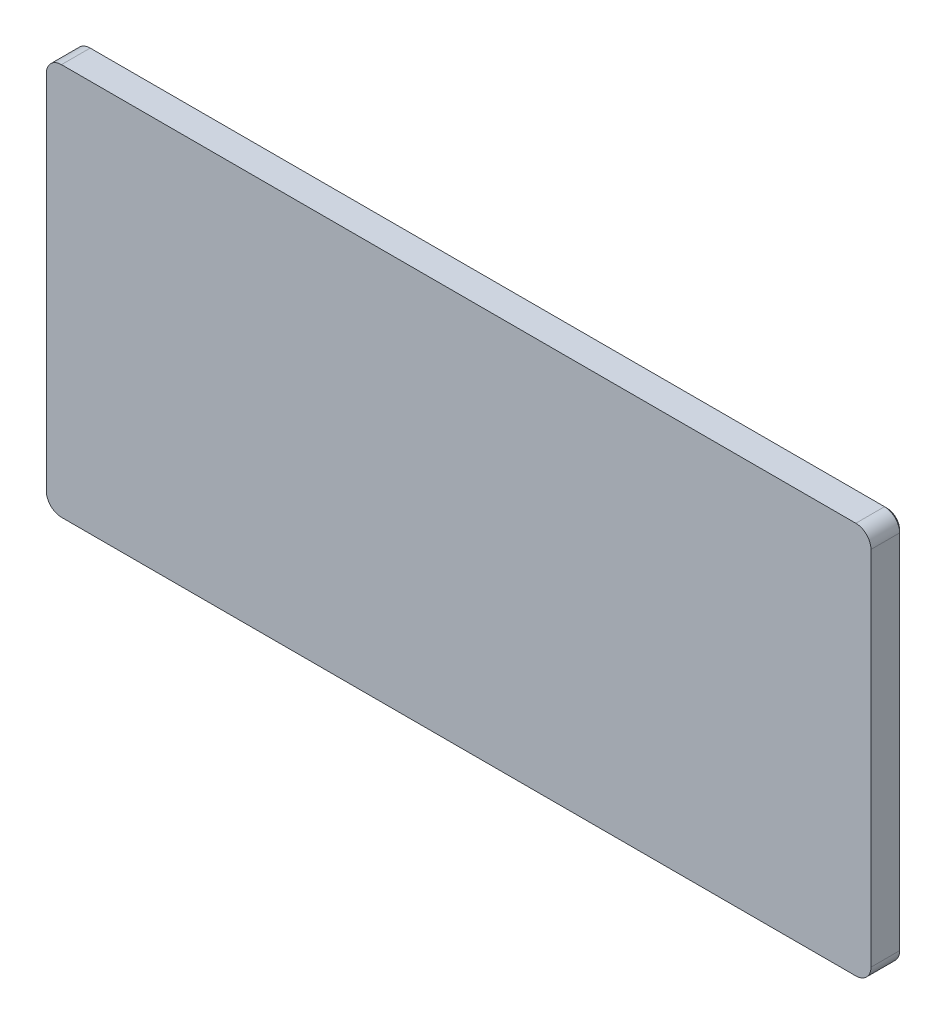
SolidWorks part; units mm, degrees
ref_plane "Front" through (0, 0, 0) normal (0, 0, 1) x (1, 0, 0)
ref_plane "Top" through (0, 0, 0) normal (0, 1, 0) x (1, 0, 0)
ref_plane "Right" through (0, 0, 0) normal (1, 0, 0) x (0, 0, -1)
sketch "Sketch1" plane through (0, 0, 0) normal (0, 0, 1) x (1, 0, 0)
  line L0 (105, 46) -> (105, -46) construction
  line L5 (101, -50) -> (-101, -50) construction
  line L6 (-105, -46) -> (-105, 46) construction
  line L7 (-101, 50) -> (101, 50) construction
  line L8 (105, 46) -> (105, -46) construction
  line L9 (101, -50) -> (-101, -50) construction
  line L10 (-105, -46) -> (-105, 46) construction
  line L11 (-101, 50) -> (101, 50) construction
  line L12 (-101, 49.85) -> (101, 49.85)
  line L13 (104.85, 46) -> (104.85, -46)
  line L14 (101, -49.85) -> (-101, -49.85)
  line L15 (-104.85, -46) -> (-104.85, 46)
  arc A0 (105, 46) -> (101, 50) centre (101, 46) ccw construction
  arc A1 (101, -50) -> (105, -46) centre (101, -46) ccw construction
  arc A2 (-105, -46) -> (-101, -50) centre (-101, -46) ccw construction
  arc A3 (-101, 50) -> (-105, 46) centre (-101, 46) ccw construction
  arc A4 (105, 46) -> (101, 50) centre (101, 46) ccw construction
  arc A5 (101, -50) -> (105, -46) centre (101, -46) ccw construction
  arc A6 (-105, -46) -> (-101, -50) centre (-101, -46) ccw construction
  arc A7 (-101, 50) -> (-105, 46) centre (-101, 46) ccw construction
  arc A8 (104.85, 46) -> (101, 49.85) centre (101, 46) ccw
  arc A9 (101, -49.85) -> (104.85, -46) centre (101, -46) ccw
  arc A10 (-104.85, -46) -> (-101, -49.85) centre (-101, -46) ccw
  arc A11 (-101, 49.85) -> (-104.85, 46) centre (-101, 46) ccw
  dimension "D1" = 0.15
extrude "Boss-Extrude1" add sketch "Sketch1" along normal up to surface (7.9 mm away)
chamfer "Chamfer1" distance 0.6 angle 45 8 edges at (104.85, 0, 0) (103.7224, 48.7224, 0) (103.7224, -48.7224, 0) (0, 49.85, 0) (0, -49.85, 0) (-103.7224, 48.7224, 0) (-103.7224, -48.7224, 0) (-104.85, 0, 0)
